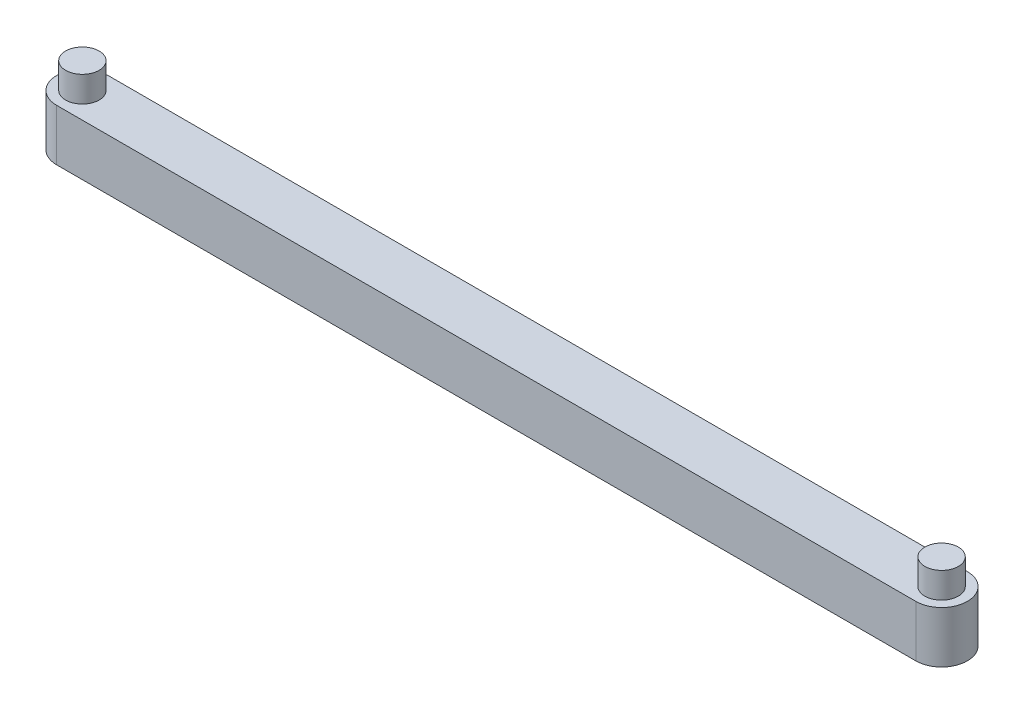
SolidWorks part; units mm, degrees
ref_plane "Front Plane" through (0, 0, 0) normal (0, 0, 1) x (1, 0, 0)
ref_plane "Top Plane" through (0, 0, 0) normal (0, 1, 0) x (1, 0, 0)
ref_plane "Right Plane" through (0, 0, 0) normal (1, 0, 0) x (0, 0, -1)
sketch "Sketch1" plane through (0, 0, 0) normal (0, 1, 0) x (1, 0, 0)
  line L0 (-250, 0) -> (250, 0) construction
  line L1 (-250, 15) -> (250, 15)
  line L2 (-250, -15) -> (250, -15)
  arc A0 (-250, 15) -> (-250, -15) centre (-250, 0) ccw
  arc A1 (250, -15) -> (250, 15) centre (250, 0) ccw
  point P2 (0, 0)
  dimension "D2" = 15
  dimension "D1" = 500
extrude "Boss-Extrude1" add sketch "Sketch1" along normal mid plane 30
sketch "Sketch2" plane through (0, 0, 0) normal (0, 1, 0) x (1, 0, 0)
  circle A0 centre (-250, 0) radius 9.75
  circle A1 centre (250, 0) radius 9.75
  dimension "D1" = 19.5
extrude "Boss-Extrude2" add sketch "Sketch2" along normal blind 30
extrude "Cut-Extrude1" cut sketch "Sketch2<2>" against normal through all
sketch "Sketch2<2>" plane through (0, 0, 0) normal (0, 1, 0) x (1, 0, 0) same geometry as "Sketch2"
extrude "Boss-Extrude3" add sketch "Sketch2<3>" against normal blind 3
sketch "Sketch2<3>" plane through (0, 0, 0) normal (0, 1, 0) x (1, 0, 0) same geometry as "Sketch2"
